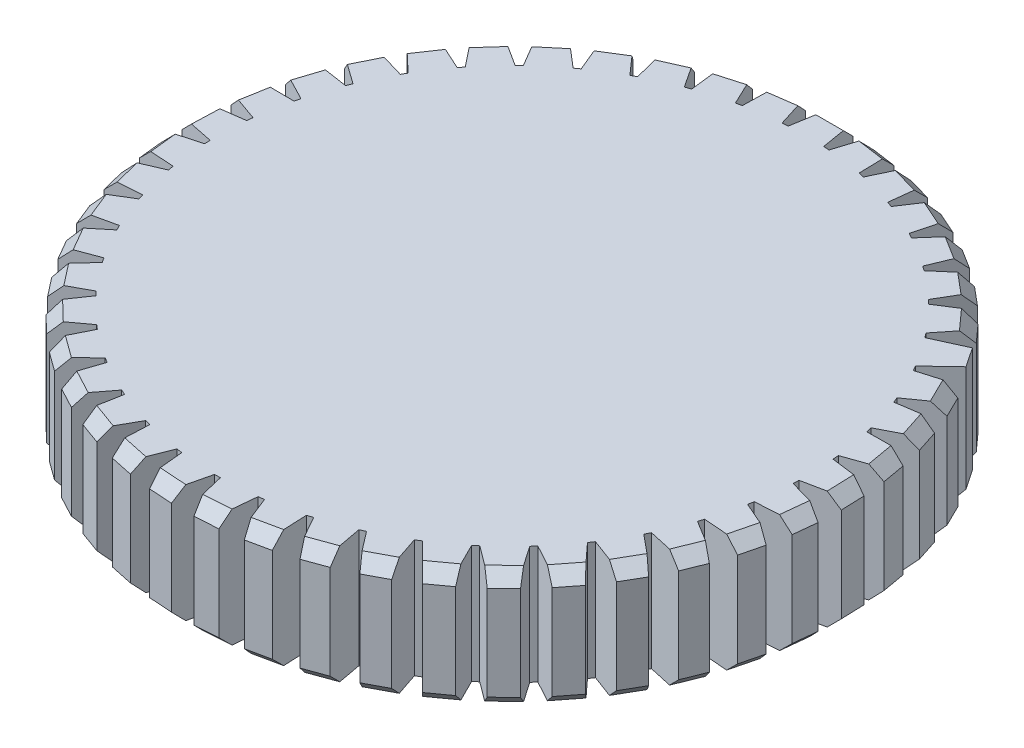
SolidWorks part; units mm, degrees
ref_plane "Front Plane" through (0, 0, 0) normal (0, 0, 1) x (1, 0, 0)
ref_plane "Top Plane" through (0, 0, 0) normal (0, 1, 0) x (1, 0, 0)
ref_plane "Right Plane" through (0, 0, 0) normal (1, 0, 0) x (0, 0, -1)
sketch "Sketch1" plane through (0, 0, 0) normal (0, 1, 0) x (1, 0, 0)
  circle A0 centre (0, 0) radius 25
  dimension "D1" = 50
extrude "Boss-Extrude1" add sketch "Sketch1" along normal blind 10
sketch "Sketch2" plane through (0, 10, 0) normal (0, 1, 0) x (1, 0, 0)
  line L0 (0, 25) -> (0, 27.955) construction
  line L1 (1, 27.955) -> (-1, 27.955)
  line L2 (-1, 27.955) -> (-1.5, 24.955)
  line L3 (1, 27.955) -> (1.5, 24.955)
  circle A0 centre (0, 0) radius 25 construction
  circle A1 centre (0, 0) radius 25
  point P9 (0, 27.9079)
  circle M4 centre (0, 0) radius 25
  dimension "D1" = 1
  dimension "D2" = 3
  dimension "D3" = 1.5
extrude "Boss-Extrude2" add sketch "Sketch2" against normal up to surface (10 mm away) contours A1 L0 L1 L2 | L0 L3 L1 M4 up to face at (0, 0, 25)
pattern_circular "CirPattern4" count 45 over 360 about axis through (0, 0, 0) along (0, 1, 0) of "Boss-Extrude2"
chamfer "Chamfer1" distance 1 angle 45 89 edges at (-25.1258, 10, -12.2546) (-25.1258, 0, -12.2546) (0, 0, -27.955) (-26.5867, 10, -8.6386) (-26.5867, 0, -8.6386) (-27.5303, 10, -4.8543) (-27.5303, 0, -4.8543) (-27.9379, 10, -0.9756) (-27.9379, 0, -0.9756) (-27.8018, 10, 2.9221) (-27.8018, 0, 2.9221) (-27.1246, 10, 6.7629) (-27.1246, 0, 6.7629) (-25.9194, 10, 10.4721) (-25.9194, 0, 10.4721) (-24.2097, 10, 13.9775) (-24.2097, 0, 13.9775) (-22.0288, 10, 17.2108) (-22.0288, 0, 17.2108) (-19.4191, 10, 20.1091) (-19.4191, 0, 20.1091) (-16.4315, 10, 22.616) (-16.4315, 0, 22.616) (-3.8906, 10, -27.6829) (-13.1241, 10, 24.6828) (-13.1241, 0, 24.6828) (-9.5612, 10, 26.2691) (-9.5612, 0, 26.2691) (-3.8906, 0, -27.6829) (-5.8122, 10, 27.3441) (-5.8122, 0, 27.3441) (-1.95, 10, 27.8869) (-1.95, 0, 27.8869) (1.95, 10, 27.8869) (1.95, 0, 27.8869) (5.8122, 10, 27.3441) (5.8122, 0, 27.3441) (9.5612, 10, 26.2691) (9.5612, 0, 26.2691) (13.1241, 10, 24.6828) (13.1241, 0, 24.6828) (16.4315, 10, 22.616) (16.4315, 0, 22.616) (19.4191, 10, 20.1091) (19.4191, 0, 20.1091) (-7.7054, 10, -26.872) (22.0288, 10, 17.2108) (22.0288, 0, 17.2108) (24.2097, 10, 13.9775) (24.2097, 0, 13.9775) (-7.7054, 0, -26.872) (25.9194, 10, 10.4721) (25.9194, 0, 10.4721) (27.1246, 10, 6.7629) (27.1246, 0, 6.7629) (27.8018, 10, 2.9221) (27.8018, 0, 2.9221) (27.9379, 10, -0.9756) (27.9379, 0, -0.9756) (27.5303, 10, -4.8543) (27.5303, 0, -4.8543) (26.5867, 10, -8.6386) (26.5867, 0, -8.6386) (25.1258, 10, -12.2546) (25.1258, 0, -12.2546) (23.1757, 0, -15.6322) (-11.3703, 10, -25.5381) (20.7746, 10, -18.7055) (20.7746, 0, -18.7055) (17.9691, 10, -21.4147) (17.9691, 0, -21.4147) (-11.3703, 0, -25.5381) (14.8139, 10, -23.7072) (14.8139, 0, -23.7072) (11.3703, 10, -25.5381) (11.3703, 0, -25.5381) (7.7054, 10, -26.872) (7.7054, 0, -26.872) (3.8906, 10, -27.6829) (3.8906, 0, -27.6829) (-14.8139, 10, -23.7072) (-14.8139, 0, -23.7072) (-17.9691, 10, -21.4147) (-17.9691, 0, -21.4147) (-20.7746, 10, -18.7055) (-20.7746, 0, -18.7055) (0, 10, -27.955) (-23.1757, 10, -15.6322) (-23.1757, 0, -15.6322)
